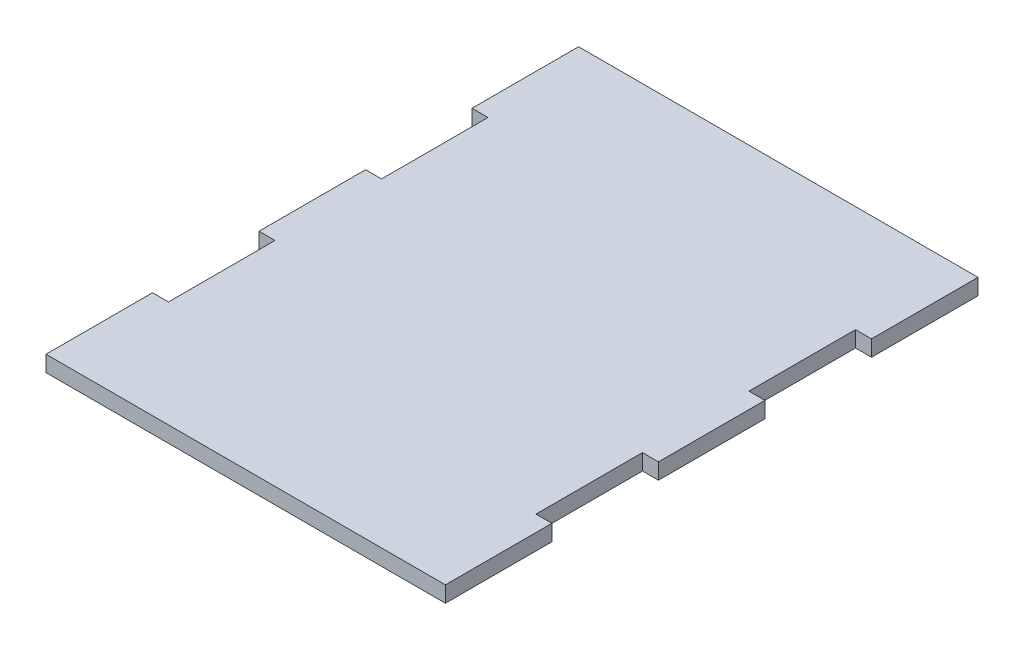
SolidWorks part; units mm, degrees
material "Pine"
ref_plane "Front Plane" through (0, 0, 0) normal (0, 0, 1) x (1, 0, 0)
ref_plane "Top Plane" through (0, 0, 0) normal (0, 1, 0) x (1, 0, 0)
ref_plane "Right Plane" through (0, 0, 0) normal (1, 0, 0) x (0, 0, -1)
sketch "Sketch1" plane through (0, 0, 0) normal (0, 1, 0) x (1, 0, 0)
  line L1 (-75, 100) -> (75, 100)
  line L2 (-75, 100) -> (-75, -100)
  line L3 (-75, -100) -> (75, -100)
  line L4 (75, 100) -> (75, -100)
  line L5 (-75, 100) -> (75, -100) construction
  line L6 (-75, -100) -> (75, 100) construction
  point P0 (0, 0)
  dimension "D1" = 150
  dimension "D2" = 200
extrude "Boss-Extrude1" add sketch "Sketch1" along normal blind 6
sketch "Sketch2" plane through (0, 6, 0) normal (0, 1, 0) x (1, 0, 0)
  line L0 (-75, 100) -> (-75, -100) construction
  line L1 (-75, 60) -> (-69, 60)
  line L2 (-75, 60) -> (-75, 20)
  line L3 (-75, 20) -> (-69, 20)
  line L4 (-69, 60) -> (-69, 20)
  line L5 (75, 100) -> (-75, 100) construction
  line L6 (69, 60) -> (69, 20)
  line L7 (69, 60) -> (75, 60)
  line L8 (75, 60) -> (75, 20)
  line L9 (69, 20) -> (75, 20)
  line L10 (69, -20) -> (69, -60)
  line L11 (69, -20) -> (75, -20)
  line L12 (75, -20) -> (75, -60)
  line L13 (69, -60) -> (75, -60)
  line L14 (-75, -20) -> (-75, -60)
  line L15 (-75, -20) -> (-69, -20)
  line L16 (-69, -20) -> (-69, -60)
  line L17 (-75, -60) -> (-69, -60)
  dimension "D1" = 40
  dimension "D2" = 40
  dimension "D3" = 6
  dimension "D4" = 2
  dimension "D5" = 2
extrude "Cut-Extrude1" cut sketch "Sketch2" against normal blind 6
